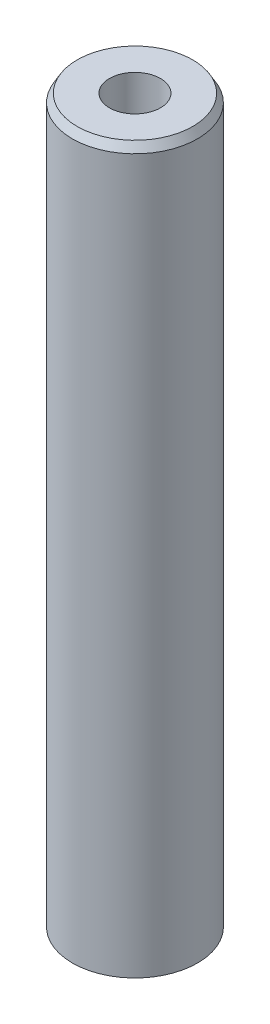
SolidWorks part; units mm, degrees
ref_plane "Front Plane" through (0, 0, 0) normal (0, 0, 1) x (1, 0, 0)
ref_plane "Top Plane" through (0, 0, 0) normal (0, 1, 0) x (1, 0, 0)
ref_plane "Right Plane" through (0, 0, 0) normal (1, 0, 0) x (0, 0, -1)
sketch "Sketch1" plane through (0, 0, 0) normal (0, 1, 0) x (1, 0, 0)
  circle A0 centre (0, 0) radius 17.5
  dimension "SHAFT_OD" = 35
extrude "Boss-Extrude1" add sketch "Sketch1" along normal blind 203.3473
sketch "Sketch2" plane through (0, 0, 0) normal (0, 1, 0) x (1, 0, 0)
  circle A0 centre (0, 0) radius 7.1308
  dimension "BORE_D" = 14.2617
extrude "Cut-Extrude1" cut sketch "Sketch2" along normal through all
chamfer "Chamfer1" distance 2.3235 angle 30 2 edges at (0, 203.3473, 17.5) (0, 0, 17.5) first distance on face at (0, 203.3473, 17.5) first distance on face at (0, 0, 7.1308)
